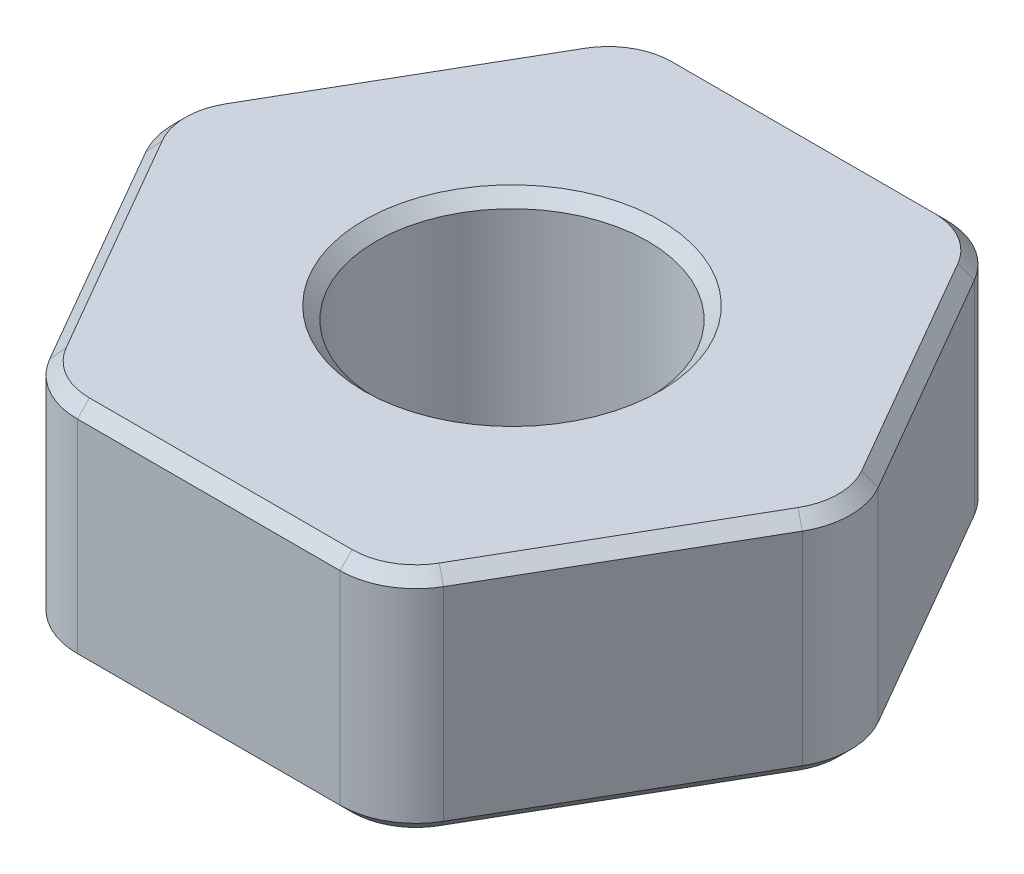
SolidWorks part; units mm, degrees
ref_plane "Front Plane" through (0, 0, 0) normal (0, 0, 1) x (1, 0, 0)
ref_plane "Top Plane" through (0, 0, 0) normal (0, 1, 0) x (1, 0, 0)
ref_plane "Right Plane" through (0, 0, 0) normal (1, 0, 0) x (0, 0, -1)
sketch "Sketch3" plane through (0, 0, 0) normal (0, 1, 0) x (1, 0, 0)
  line L1 (1.8331, 3.175) -> (-1.8331, 3.175)
  line L2 (-1.8331, 3.175) -> (-3.6662, 0)
  line L3 (-3.6662, 0) -> (-1.8331, -3.175)
  line L4 (-1.8331, -3.175) -> (1.8331, -3.175)
  line L5 (1.8331, -3.175) -> (3.6662, 0)
  line L6 (3.6662, 0) -> (1.8331, 3.175)
  circle A0 centre (0, 0) radius 3.6662 construction
  circle A1 centre (0, 0) radius 1.4224
  circle A2 centre (0, 0) radius 3.175 construction
  dimension "D1" = 2.8448
  dimension "D2" = 6.35
extrude "Boss-Extrude1" add sketch "Sketch3" along normal mid plane 2.3813
fillet "Fillet1" radius 0.7937 6 edges at (3.6662, 0, 0) (1.8331, 0, 3.175) (-3.6662, 0, 0) (-1.8331, 0, -3.175) (1.8331, 0, -3.175) (-1.8331, 0, 3.175)
chamfer "Chamfer1" distance 0.127 angle 45 26 edges at (0, -1.1906, 1.4224) (0, 1.1906, 1.4224) (0, 1.1906, -3.175) (-1.7717, 1.1906, -3.0687) (1.7717, 1.1906, -3.0687) (-2.7496, 1.1906, -1.5875) (2.7496, 1.1906, -1.5875) (-3.5434, 1.1906, 0) (3.5434, 1.1906, 0) (-2.7496, 1.1906, 1.5875) (2.7496, 1.1906, 1.5875) (-1.7717, 1.1906, 3.0687) (1.7717, 1.1906, 3.0687) (0, 1.1906, 3.175) (0, -1.1906, -3.175) (-1.7717, -1.1906, -3.0687) (1.7717, -1.1906, -3.0687) (-2.7496, -1.1906, -1.5875) (2.7496, -1.1906, -1.5875) (-3.5434, -1.1906, 0) (3.5434, -1.1906, 0) (-2.7496, -1.1906, 1.5875) (2.7496, -1.1906, 1.5875) (-1.7717, -1.1906, 3.0687) (1.7717, -1.1906, 3.0687) (0, -1.1906, 3.175)
